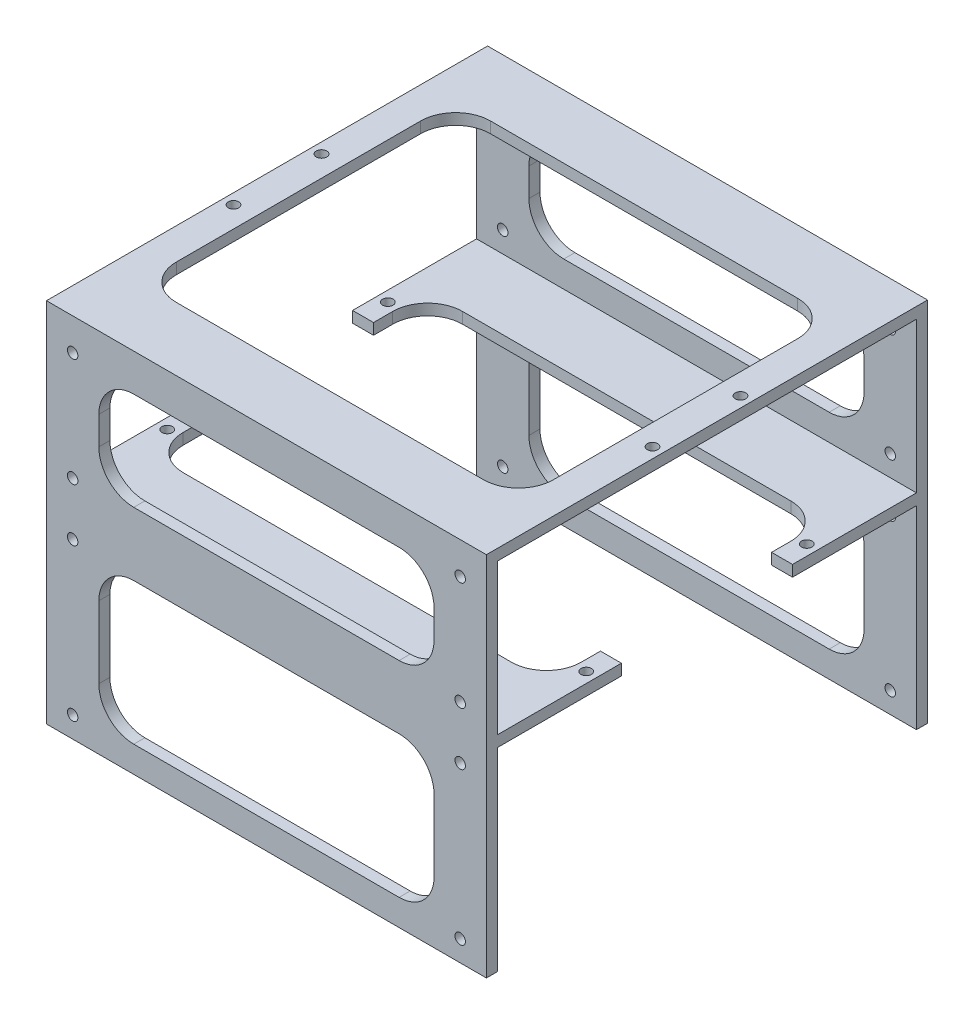
SolidWorks part; units mm, degrees
ref_plane "Front Plane" through (0, 0, 0) normal (0, 0, 1) x (1, 0, 0)
ref_plane "Top Plane" through (0, 0, 0) normal (0, 1, 0) x (1, 0, 0)
ref_plane "Right Plane" through (0, 0, 0) normal (1, 0, 0) x (0, 0, -1)
sketch "Sketch1" plane through (0, 0, 0) normal (1, 0, 0) x (0, 0, -1)
  line L0 (-95, 46.4295) -> (-95, -3.5705)
  line L1 (-43.5, 92.6795) -> (-95, 92.6795)
  line L3 (-43.5, 96.4295) -> (-100, 96.4295)
  line L4 (-100, 86.4295) -> (-100, 96.4295)
  line L5 (-100, 96.4295) -> (-90, 96.4295)
  line L6 (-100, 96.4295) -> (-100, -8.5705)
  line L7 (-100, -8.5705) -> (-90, -8.5705)
  line L8 (-95, 92.6795) -> (-95, 50.1795)
  line L9 (-95, 50.1795) -> (-59.5, 50.1795)
  line L11 (-95, 46.4295) -> (-59.5, 46.4295)
  line L12 (-59.5, 50.1795) -> (-59.5, 46.4295)
  line L13 (-90, -8.5705) -> (-35, -8.5705)
  line L15 (-95, -3.5705) -> (-35, -3.5705)
  line L16 (-35, -8.5705) -> (-35, -3.5705)
  line L18 (-43.5, 96.4295) -> (-35, 96.4295)
  line L20 (-43.5, 92.6795) -> (-35, 92.6795)
  line L21 (-35, 96.4295) -> (-35, 92.6795)
  dimension "D1" = 3.75
  dimension "D2" = 56.5
  dimension "D3" = 5
  dimension "D4" = 105
  dimension "D5" = 55
  dimension "D6" = 3.75
  dimension "D8" = 5
  dimension "D9" = 65
extrude "Boss-Extrude1" add sketch "Sketch1" along normal blind 126 contours L13 L16 L15 L0 L11 L12 L9 L8 L1 L3 L4 L6 L7 region at (0, 21.4295, 96.2349)
sketch "Sketch2" plane through (0, 96.4295, 0) normal (0, 1, 0) x (1, 0, 0)
  line L0 (0, -35.75) -> (0, 35.75) construction
  line L1 (126, -35) -> (0, -35) construction
  circle A0 centre (3, -47.6) radius 1.5
  circle A1 centre (123, -47.6) radius 1.5
  dimension "D1" = 3
  dimension "D2" = 3
  dimension "D3" = 120
  dimension "D4" = 3
  dimension "D5" = 12.6
extrude "Cut-Extrude1" cut sketch "Sketch2" against normal up to surface (46.25 mm away) contours A1 | A0 up to face at (63, 50.1795, 77.25)
sketch "Sketch3" plane through (0, 50.1795, 0) normal (0, 1, 0) x (1, 0, 0)
  line L3 (126, -35) -> (126, -100) construction
  line L4 (0, -35.75) -> (0, 35.75) construction
  line L5 (126, -35) -> (0, -35) construction
  line L7 (6, -95) -> (6, -59.5)
  line L8 (6, -65) -> (6, -35)
  line L9 (16, -75) -> (110, -75)
  line L10 (120, -95) -> (120, -59.5)
  line L11 (120, -65) -> (120, -35)
  line L12 (6, -35) -> (120, -35)
  circle A0 centre (3, -66.6) radius 1.5
  circle A1 centre (123, -66.6) radius 1.5
  arc A3 (16, -75) -> (6, -65) centre (16, -65) cw
  arc A4 (110, -75) -> (120, -65) centre (110, -65) ccw
  circle A8 centre (3, -47.6) radius 1.5 construction
  dimension "D1" = 3
  dimension "D2" = 3
  dimension "D4" = 3
  dimension "D5" = 19
  dimension "D8" = 10
  dimension "D9" = 10
  dimension "D3" = 3
  dimension "D6" = 6
  dimension "D10" = 40
  dimension "D7" = 6
extrude "Cut-Extrude3" cut sketch "Sketch3" against normal up to surface (53.75 mm away) contours A0 | A1 | L11 L12 L8 A3 L9 A4 up to face at (63, -3.5705, 65)
ref_plane "Plane1" through (0, 0, 35) normal (0, 0, -1) x (-1, 0, 0)
mirror "Mirror2" about plane through (0, 0, 35) normal (0, 0, -1) of "Cut-Extrude1", "Cut-Extrude3", "Boss-Extrude1"
sketch "Sketch4" plane through (0, 96.4295, 0) normal (0, 1, 0) x (1, 0, 0)
  line L0 (9, -35) -> (9, -70)
  line L2 (19, -80) -> (106.9997, -80)
  line L3 (116.9997, -70) -> (116.9997, -35)
  line L4 (9, -35) -> (116.9997, -35)
  line L5 (63, -100) -> (62.9998, -80) construction
  line L6 (9, -35) -> (116.9997, -35)
  line L7 (126, -100) -> (0, -100) construction
  line L9 (126, -35) -> (0, -35) construction
  line L10 (126, -100) -> (126, 30) construction
  line L11 (0, -57.75) -> (0, 57.75) construction
  line L12 (55, -35) -> (-55, -35) construction
  circle A0 centre (3, -47.6) radius 1.5 construction
  arc A2 (106.9997, -80) -> (116.9997, -70) centre (106.9997, -70) ccw
  arc A3 (19, -80) -> (9, -70) centre (19, -70) cw
  dimension "D1" = 6
  dimension "D4" = 10
  dimension "D2" = 45
extrude "Cut-Extrude6" cut sketch "Sketch4" against normal up to surface (46.25 mm away) contours L4 L3 A2 L2 A3 L0 up to face at (3, 50.1795, 68.1)
mirror "Mirror5" about plane through (0, 0, 35) normal (0, 0, -1) of "Cut-Extrude6"
sketch "Sketch5" plane through (126, 0, 0) normal (1, 0, 0) x (0, 0, -1)
  line L0 (-35, 96.4295) -> (-35, 93.2545) construction
  line L1 (-100, 96.4295) -> (30, 96.4295) construction
  line L2 (-100, -8.5705) -> (30, -8.5705) construction
  line L3 (-95, 46.4295) -> (-95, -3.5705) construction
  line L4 (-95, -3.5705) -> (25, -3.5705)
  line L5 (-95, -3.5705) -> (-95, -8.5705)
  line L6 (-95, -8.5705) -> (25, -8.5705)
  line L8 (-100, 96.4295) -> (-98.175, 96.4295)
  line L9 (-100, 96.4295) -> (-100, -8.5705)
  line L10 (-100, -8.5705) -> (-98.175, -8.5705)
  line L11 (-98.175, 93.2545) -> (-98.175, -8.5705)
  line L12 (-59.5, 50.1795) -> (-59.5, 46.4295) construction
  line L13 (-95, 92.6795) -> (25, 92.6795)
  line L14 (-95, 92.6795) -> (-95, 93.2545)
  line L15 (-95, 93.2545) -> (25, 93.2545)
  line L17 (-95, 46.4295) -> (-59.5, 46.4295)
  line L18 (-95, 46.4295) -> (-95, 47.0045)
  line L19 (-95, 47.0045) -> (-59.5, 47.0045)
  line L20 (-59.5, 46.4295) -> (-59.5, 47.0045)
  line L21 (-95, 50.1795) -> (-59.5, 50.1795) construction
  line L22 (25, 92.6795) -> (25, 93.2545)
  line L23 (25, -3.5705) -> (25, -8.5705)
  line L24 (-10.5, 46.4295) -> (-10.5, 47.0045)
  line L25 (25, 47.0045) -> (-10.5, 47.0045)
  line L26 (25, 46.4295) -> (25, 47.0045)
  line L27 (25, 46.4295) -> (-10.5, 46.4295)
  line L28 (28.175, 93.2545) -> (28.175, -8.5705)
  line L29 (30, -8.5705) -> (28.175, -8.5705)
  line L30 (30, 96.4295) -> (30, -8.5705)
  line L31 (30, 96.4295) -> (28.175, 96.4295)
  line L32 (-35, 92.6795) -> (-35, -3.5705) construction
  line L33 (-98.175, 93.2545) -> (-97.175, 93.2545)
  line L43 (28.175, 96.4295) -> (27.175, 96.4295)
  line L45 (28.175, 93.2545) -> (27.175, 93.2545)
  line L46 (27.175, 96.4295) -> (27.175, 93.2545)
  line L47 (-97.175, 96.4295) -> (-97.175, 93.2545)
  line L48 (-98.175, 96.4295) -> (-97.175, 96.4295)
  dimension "D1" = 3.175
  dimension "D2" = 3.175
  dimension "D3" = 3.175
  dimension "D4" = 1
extrude "Cut-Extrude7" cut sketch "Sketch5" against normal through all
sketch "Sketch6" plane through (0, 0, 95) normal (0, 0, -1) x (-1, 0, 0)
  line L0 (-62.9998, 93.2545) -> (-63, 50.1795) construction
  line L1 (-106.9997, 93.2545) -> (-19, 93.2545) construction
  line L2 (-126, 50.1795) -> (0, 50.1795) construction
  line L3 (0, 93.2545) -> (-126, 93.2545) construction
  line L4 (-100.9998, 85.7545) -> (-25, 85.7545)
  line L5 (-110.9998, 75.7545) -> (-110.9998, 67.6795)
  line L6 (-100.9998, 57.6795) -> (-25, 57.6795)
  line L7 (-15, 75.7545) -> (-15, 67.6795)
  line L8 (-110.9998, 85.7545) -> (-15, 57.6795) construction
  line L9 (-110.9998, 57.6795) -> (-15, 85.7545) construction
  line L10 (0, 93.2545) -> (0, 50.1795) construction
  line L11 (-63, 47.0045) -> (-63, -8.5705) construction
  line L12 (-110, 47.0045) -> (-16, 47.0045) construction
  line L13 (0, -8.5705) -> (-126, -8.5705) construction
  line L14 (0, 47.0045) -> (0, -8.5705) construction
  line L15 (-101, 39.5045) -> (-25, 39.5045)
  line L16 (-111, 29.5045) -> (-111, 8.9295)
  line L17 (-101, -1.0705) -> (-25, -1.0705)
  line L18 (-15, 29.5045) -> (-15, 8.9295)
  line L19 (-111, 39.5045) -> (-15, -1.0705) construction
  line L20 (-111, -1.0705) -> (-15, 39.5045) construction
  line L21 (0, 47.0045) -> (-126, 47.0045) construction
  arc A0 (-25, 39.5045) -> (-15, 29.5045) centre (-25, 29.5045) cw
  arc A1 (-25, -1.0705) -> (-15, 8.9295) centre (-25, 8.9295) ccw
  arc A2 (-111, 8.9295) -> (-101, -1.0705) centre (-101, 8.9295) ccw
  arc A3 (-101, 39.5045) -> (-111, 29.5045) centre (-101, 29.5045) ccw
  arc A4 (-110.9998, 67.6795) -> (-100.9998, 57.6795) centre (-100.9998, 67.6795) ccw
  arc A5 (-100.9998, 85.7545) -> (-110.9998, 75.7545) centre (-100.9998, 75.7545) ccw
  arc A6 (-25, 57.6795) -> (-15, 67.6795) centre (-25, 67.6795) ccw
  arc A7 (-25, 85.7545) -> (-15, 75.7545) centre (-25, 75.7545) cw
  point P6 (-62.9999, 71.717)
  point P21 (-63, 19.217)
  dimension "D5" = 10
  dimension "D1" = 7.5
  dimension "D2" = 15
  dimension "D3" = 15
  dimension "D4" = 7.5
extrude "Cut-Extrude8" cut sketch "Sketch6" against normal through all and the other way through all
sketch "Sketch7" plane through (0, 0, 98.175) normal (0, 0, 1) x (1, 0, 0)
  line L0 (63, 93.2545) -> (63, -1.0705) construction
  line L1 (0, 93.2545) -> (126, 93.2545) construction
  line L2 (101, -1.0705) -> (25, -1.0705) construction
  line L3 (118.5, 93.2545) -> (118.5, -8.5705) construction
  line L5 (126, 93.2545) -> (126, 50.1795) construction
  line L6 (0, -8.5705) -> (126, -8.5705) construction
  line L7 (126, 50.1795) -> (0, 50.1795) construction
  line L8 (110, 47.0045) -> (120, 47.0045) construction
  line L9 (7.5, 93.2545) -> (7.5, -8.5705) construction
  circle A0 centre (118.5, 87.2545) radius 1.5
  circle A1 centre (118.5, 56.1795) radius 1.5
  circle A2 centre (118.5, 41.0045) radius 1.5
  circle A3 centre (118.5, -2.5705) radius 1.5
  circle A4 centre (7.5, -2.5705) radius 1.5
  circle A5 centre (7.5, 41.0045) radius 1.5
  circle A6 centre (7.5, 56.1795) radius 1.5
  circle A7 centre (7.5, 87.2545) radius 1.5
  dimension "D2" = 6
  dimension "D3" = 3
  dimension "D5" = 3
  dimension "D7" = 3
  dimension "D8" = 3
  dimension "D1" = 7.5
  dimension "D4" = 6
  dimension "D6" = 6
  dimension "D9" = 6
extrude "Cut-Extrude9" cut sketch "Sketch7" against normal through all and the other way through all
sketch "Sketch8" plane through (126, 0, 0) normal (1, 0, 0) x (0, 0, -1)
  line L0 (-97.175, 96.4295) -> (-97.175, 93.2545)
  line L1 (-97.175, 93.2545) -> (-98.175, 93.2545)
  line L2 (-98.175, 93.2545) -> (-98.175, 96.4295)
  line L3 (-98.175, 96.4295) -> (-97.175, 96.4295)
  line L4 (28.175, 93.2545) -> (27.175, 93.2545)
  line L5 (27.175, 93.2545) -> (27.175, 96.4295)
  line L6 (27.175, 96.4295) -> (28.175, 96.4295)
  line L7 (28.175, 96.4295) -> (28.175, 93.2545)
extrude "Boss-Extrude2" add sketch "Sketch8" against normal up to surface (126 mm away) up to face at (0, 55.342, 35)
